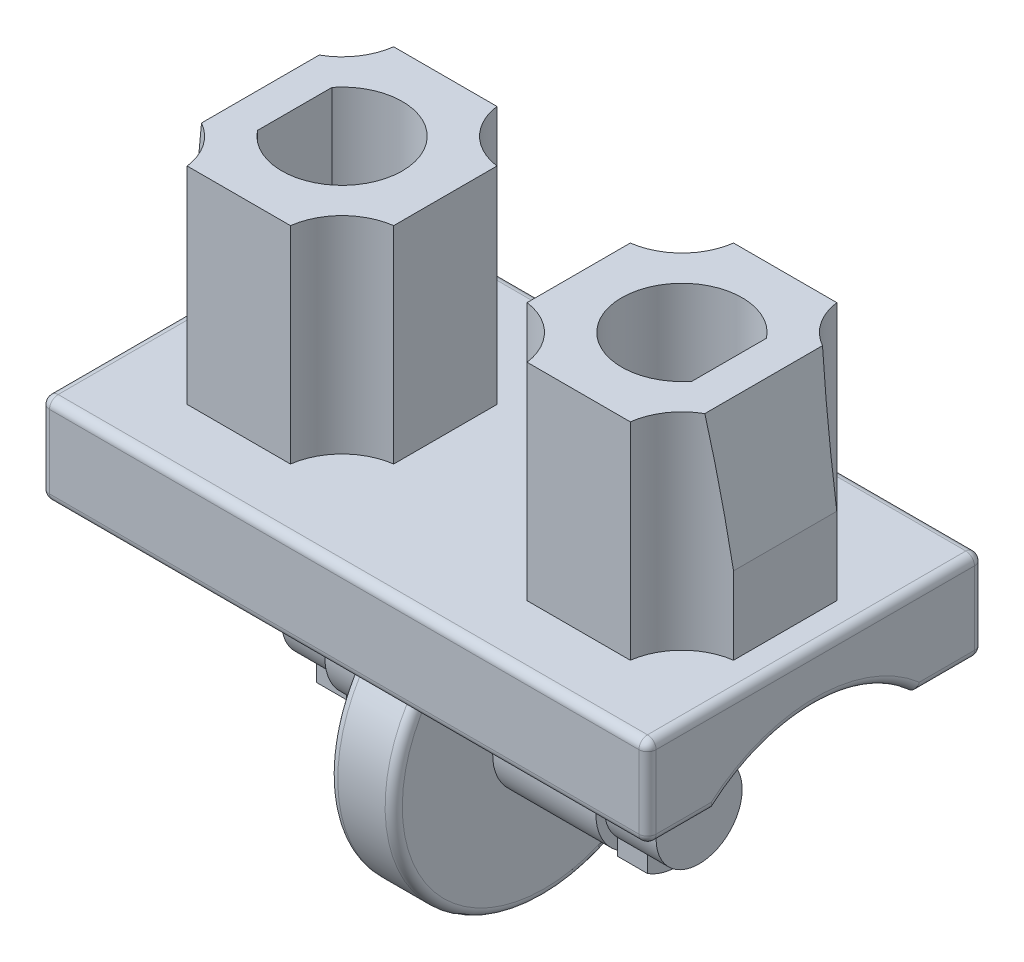
SolidWorks part; units mm, degrees
ref_plane "Plan de face" through (0, 0, 0) normal (0, 0, 1) x (1, 0, 0)
ref_plane "Plan de dessus" through (0, 0, 0) normal (0, 1, 0) x (1, 0, 0)
ref_plane "Plan de droite" through (0, 0, 0) normal (1, 0, 0) x (0, 0, -1)
sketch "Sketch1" plane through (0, 0, 0) normal (1, 0, 0) x (0, 0, -1)
  line L0 (2.3431, -2.1) -> (3.9, -2.1)
  line L1 (-3.9, 0) -> (3.9, 0)
  line L2 (-3.9, 0) -> (-3.9, -2.1)
  line L3 (-3.9, -2.1) -> (-2.3431, -2.1)
  line L4 (3.9, 0) -> (3.9, -2.1)
  circle A0 centre (0, -4.7) radius 3.5
  dimension "D3" = 7
  dimension "D4" = 4.7
  dimension "D1" = 2.1
  dimension "D2" = 7.8
extrude "Boss-Extrude1" add sketch "Sketch1" along normal blind 7.05 contours A0 L0 L4 L1 L2 L3 region at (0, -0.9029, 0)
extrude "Boss-Extrude2" add sketch "Sketch1<5>" along normal blind 0.75 contours A0 region at (0, -4.7, 0)
sketch "Sketch1<5>" plane through (0, 0, 0) normal (1, 0, 0) x (0, 0, -1) same geometry as "Sketch1"
sketch "Sketch2" plane through (0.75, 0, 0) normal (1, 0, 0) x (0, 0, -1)
  circle A0 centre (0, -4.7) radius 1.2
  dimension "D1" = 2.4
extrude "Boss-Extrude3" add sketch "Sketch2" along normal blind 2.4
sketch "Sketch3" plane through (3.15, 0, 0) normal (1, 0, 0) x (0, 0, -1)
  circle A0 centre (0, -4.7) radius 1
  dimension "D1" = 2
extrude "Boss-Extrude4" add sketch "Sketch3" along normal blind 1.2
sketch "Sketch4" plane through (4.35, 0, 0) normal (1, 0, 0) x (0, 0, -1)
  line L0 (-0.6614, -3.95) -> (0.6614, -3.95)
  circle A0 centre (0, -4.7) radius 1 construction
  arc A1 (0.6614, -3.95) -> (-0.6614, -3.95) centre (0, -4.7) ccw
  dimension "D1" = 0.75
extrude "Cut-Extrude1" cut sketch "Sketch4" against normal blind 1.2
sketch "Sketch5" plane through (3.15, 0, 0) normal (1, 0, 0) x (0, 0, -1)
  line L0 (0, -4.8379) -> (0, -8.6328) construction
  line L1 (-0.7, -5.4141) -> (-0.7, -5.7941)
  line L3 (0.7, -5.4141) -> (0.7, -5.7941)
  arc A0 (-0.6614, -3.95) -> (0.6614, -3.95) centre (0, -4.7) ccw construction
  arc A1 (-0.6614, -3.95) -> (0.6614, -3.95) centre (0, -4.7) ccw construction
  arc A2 (-0.7, -5.4141) -> (0.7, -5.4141) centre (0, -4.7) ccw
  arc A3 (-0.7, -5.7941) -> (0.7, -5.7941) centre (0, -4.7) ccw
  dimension "D1" = 0.38
  dimension "D2" = 1.4
extrude "Boss-Extrude5" add sketch "Sketch5" along normal blind 0.7
sketch "Sketch6" plane through (0, 0, 0) normal (0, 1, 0) x (1, 0, 0)
  line L0 (1.55, 2.4) -> (0.4302, 3.5198) construction
  line L1 (1.55, -2.4) -> (6.35, -2.4)
  line L2 (1.55, -2.4) -> (1.55, 2.4)
  line L3 (1.55, 2.4) -> (6.35, 2.4)
  line L4 (6.35, -2.4) -> (6.35, 2.4)
  line L5 (1.55, -2.4) -> (6.35, 2.4) construction
  line L6 (1.55, 2.4) -> (6.35, -2.4) construction
  arc A0 (2.75, 2.4) -> (1.55, 1.2) centre (1.3626, 2.5874) cw
  arc A1 (6.35, 1.2) -> (5.15, 2.4) centre (6.5374, 2.5874) cw
  arc A2 (5.15, -2.4) -> (6.35, -1.2) centre (6.5374, -2.5874) cw
  arc A3 (1.55, -1.2) -> (2.75, -2.4) centre (1.3626, -2.5874) cw
  point P0 (3.95, 0)
  point P22 (3.95, 0)
  dimension "D5" = 1.4
  dimension "D1" = 4.8
  dimension "D2" = 4.8
  dimension "D3" = 1.55
  dimension "D4" = 1.2
  dimension "D6" = 4
extrude "Boss-Extrude6" add sketch "Sketch6" along normal blind 4.8 contours L2 A3 L1 A2 L4 A1 L3 A0 region at (3.95, 0, 0)
sketch "Sketch7" plane through (0, 4.8, 0) normal (0, 1, 0) x (1, 0, 0)
  line L0 (5.15, 2.4) -> (2.75, -2.4) construction
  line L1 (5.05, 0.866) -> (5.05, -0.866)
  line L2 (6.35, -1.2) -> (6.35, 1.2) construction
  arc A0 (5.05, 0.866) -> (5.05, -0.866) centre (3.95, 0) ccw
  dimension "D1" = 2.8
  dimension "D2" = 1.3
extrude "Cut-Extrude2" cut sketch "Sketch7" against normal blind 4.8
sketch "Sketch8" plane through (0, 0, 2.4) normal (0, 0, 1) x (1, 0, 0)
  line L0 (5.85, 4.8) -> (6.35, 4.8)
  line L1 (6.35, 4.8) -> (5.15, 4.8) construction
  line L2 (6.35, 4.8) -> (6.35, 1.8)
  line L3 (6.35, 4.8) -> (6.35, 0) construction
  line L4 (6.35, 1.8) -> (5.85, 4.8)
  dimension "D1" = 3
  dimension "D2" = 0.5
extrude "Cut-Extrude3" cut sketch "Sketch8" against normal through all
fillet "Fillet1" radius 0.2 11 edges at (7.05, -2.1, 3.1215) (7.05, -1.05, 3.9) (7.05, 0, 0) (7.05, -1.05, -3.9) (7.05, -2.1, -3.1215) (7.05, -1.2, 0) (3.525, 0, -3.9) (3.525, -2.1, -3.9) (3.525, 0, 3.9) (3.525, -2.1, 3.9) (0.75, -8.2, 0)
mirror "Mirror1" about plane through (0, 0, 0) normal (1, 0, 0) of bodies 109
